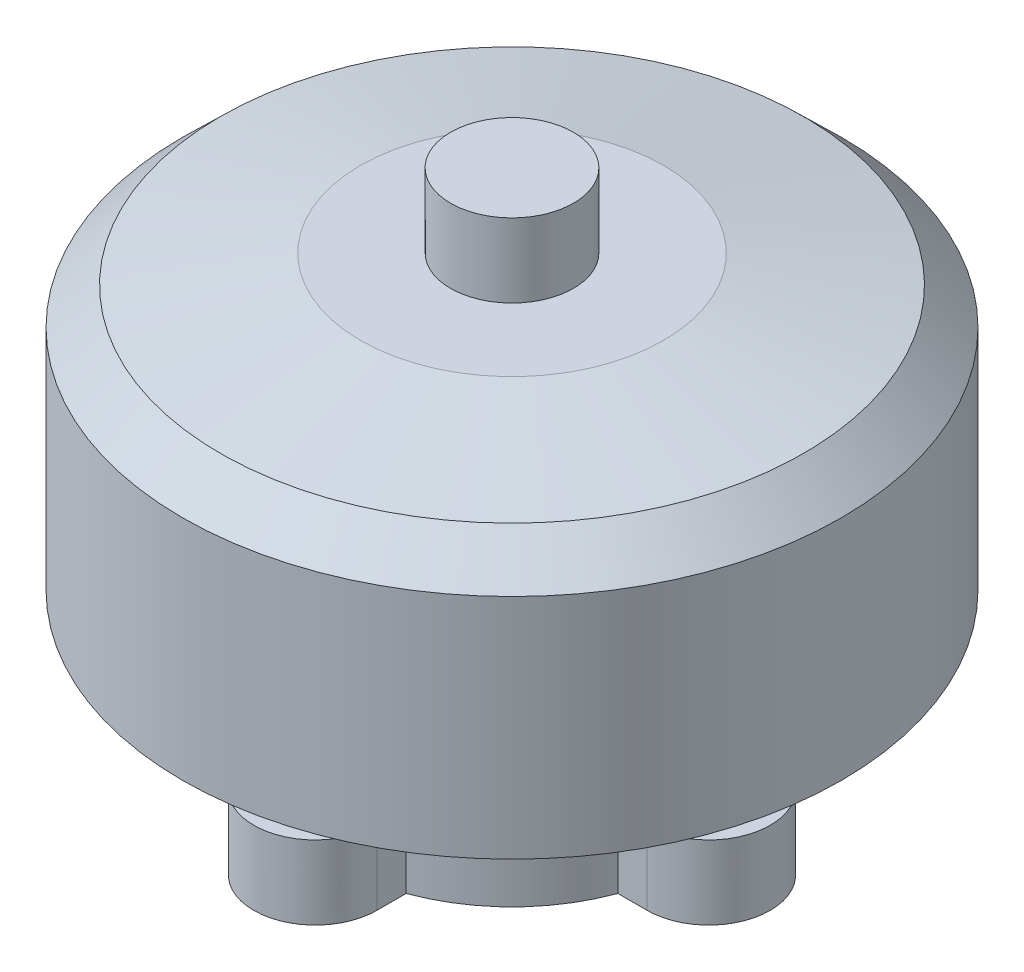
SolidWorks part; units mm, degrees
ref_plane "Спереди" through (0, 0, 0) normal (0, 0, 1) x (1, 0, 0)
ref_plane "Сверху" through (0, 0, 0) normal (0, 1, 0) x (1, 0, 0)
ref_plane "Справа" through (0, 0, 0) normal (1, 0, 0) x (0, 0, -1)
sketch "Эскиз1" plane through (0, 0, 0) normal (0, 1, 0) x (1, 0, 0)
  line L0 (0, 8) -> (0, 6) construction
  line L1 (2.5, 8) -> (2.5, 6)
  line L2 (-2.5, 8) -> (-2.5, 6)
  line L3 (8, 2.5) -> (6, 2.5)
  line L4 (8, -2.5) -> (6, -2.5)
  line L5 (8, 0) -> (6, 0) construction
  line L6 (2.5, -8) -> (2.5, -6)
  line L7 (-2.5, -8) -> (-2.5, -6)
  line L8 (0, -8) -> (0, -6) construction
  line L9 (-8, -2.5) -> (-6, -2.5)
  line L10 (-8, 2.5) -> (-6, 2.5)
  line L11 (-8, 0) -> (-6, 0) construction
  circle A0 centre (0, 0) radius 8 construction
  circle A1 centre (0, 8) radius 1.25
  circle A2 centre (8, 0) radius 1.25
  circle A3 centre (0, -8) radius 1.25
  circle A4 centre (-8, 0) radius 1.25
  circle A5 centre (0, 0) radius 6
  circle A6 centre (0, 0) radius 7.25
  arc A7 (2.5, 8) -> (-2.5, 8) centre (0, 8) ccw
  arc A8 (-2.5, 6) -> (2.5, 6) centre (0, 6) ccw
  arc A9 (8, -2.5) -> (8, 2.5) centre (8, 0) ccw
  arc A10 (6, 2.5) -> (6, -2.5) centre (6, 0) ccw
  arc A11 (-2.5, -8) -> (2.5, -8) centre (0, -8) ccw
  arc A12 (2.5, -6) -> (-2.5, -6) centre (0, -6) ccw
  arc A13 (-8, 2.5) -> (-8, -2.5) centre (-8, 0) ccw
  arc A14 (-6, -2.5) -> (-6, 2.5) centre (-6, 0) ccw
  point P13 (0, 7)
  point P23 (7, 0)
  point P30 (0, -7)
  point P37 (-7, 0)
  point P43 (0, 0)
  dimension "D1" = 16
  dimension "D2" = 2.5
  dimension "D3" = 12
  dimension "D4" = 14.5
  dimension "D5" = 2.5
  dimension "D6" = 4
extrude "Бобышка-Вытянуть1" add sketch "Эскиз1" along normal blind 3 contours A14 L9 A6 L7 A12 A5 | L10 A13 L9 A6 A4 | A5 A8 L1 A6 A1 L2 | L1 A7 L2 A6 A1 | A10 L3 A6 L1 A8 A5 | A14 A5 A8 L2 A6 L10 | L6 A12 A5 L7 A6 A3 | L9 A14 A5 L10 A6 A4 | L3 A10 A5 L4 A6 A2 | A12 L6 A6 L4 A10 A5 | L4 A9 L3 A6 A2 | L7 A11 L6 A6 A3 region at (2.4378, 0, -7.4027) region at (4.5855, 0, -4.5855) region at (0, 0, -6.3965) region at (6.3965, 0, 0) region at (7.4027, 0, -2.4378) region at (-4.5855, 0, -4.5855) region at (-7.0996, 0, -1.7504) region at (-6.3965, 0, 0) region at (4.5855, 0, 4.5855) region at (0, 0, 6.3965) region at (-4.5855, 0, 4.5855) region at (2.4378, 0, 7.4027)
cosmetic thread "Условное изображение резьбы1" parameters "D2"=3
cosmetic thread "Условное изображение резьбы2" parameters "D2"=3
cosmetic thread "Условное изображение резьбы3" parameters "D2"=3
cosmetic thread "Условное изображение резьбы4" parameters "D2"=3
sketch "Эскиз6" plane through (0, 0, 0) normal (0, 0, 1) x (1, 0, 0)
  line L0 (37.7821, 505.6995) -> (251.7821, 505.6995) construction
sketch "Эскиз2" plane through (0, 0, 0) normal (1, 0, 0) x (0, 0, -1)
  line L0 (6, 3) -> (4.2, 4.5)
  line L1 (6, 3) -> (-6, 3) construction
  line L2 (6.8053, 3) -> (2.5, 3) construction
  line L3 (4.2, 4.5) -> (0, 4.5)
  line L4 (0, 4.5) -> (0, 5.5)
  line L5 (0, 5.5) -> (3.8053, 5.5)
  line L6 (3.8053, 5.5) -> (6.8053, 3)
  line L7 (-6, 0) -> (6, 0) construction
  line L8 (6, 3) -> (6.8053, 3)
  dimension "D1" = 4.5
  dimension "D2" = 4.2
  dimension "D3" = 1
revolve "Повернуть1" add sketch "Эскиз2" angle 360 about L4
sketch "Эскиз3" plane through (0, 4.5, 0) normal (0, -1, 0) x (1, 0, 0)
  circle A0 centre (0, 0) radius 1.25
  dimension "D1" = 2.5
extrude "Вырез-Вытянуть1" cut sketch "Эскиз3" against normal through all
sketch "Эскиз4" plane through (0, 0, 2.5) normal (0, 0, 1) x (1, 0, 0)
  line L0 (8.0234, 3) -> (2.8689, 5.5)
  line L1 (9.25, 3) -> (6.7969, 3) construction
  line L2 (3.8053, 5.5) -> (-3.8053, 5.5) construction
  line L4 (6.8053, 3) -> (8.0234, 3)
  line L5 (6.8053, 3) -> (6.3295, 3)
  line L6 (6.3295, 3) -> (2.8689, 5.5)
extrude "Бобышка-Вытянуть2" add sketch "Эскиз4" against normal blind 0.75
mirror "Зеркальное отражение1" about plane through (0, 0, 0) normal (0, 0, 1) of "Бобышка-Вытянуть2"
pattern_circular "Круговой массив1" count 4 over 360 about axis through (0, 5.5, 0) along (0, -1, 0) of "Зеркальное отражение1"
sketch "Эскиз7" plane through (0, 0, 0) normal (0, 0, 1) x (1, 0, 0)
  line L0 (5.3632, 4.2902) -> (5.3632, 6.0305)
  line L1 (8.0234, 3) -> (2.8689, 5.5) construction
  line L2 (5.3632, 6.0305) -> (13.4, 6.0305)
  line L3 (13.4, 6.0305) -> (13.4, 15.2805)
  line L4 (13.4, 15.2805) -> (11.8618, 16.7778)
  line L5 (11.8618, 16.7778) -> (6.1633, 17.9076)
  line L6 (6.1633, 17.9076) -> (0, 17.9076)
  line L7 (0, 17.9076) -> (0, 4.2902)
  line L8 (0, 4.2902) -> (5.3632, 4.2902)
  dimension "D1" = 13.4
  dimension "D2" = 9.25
revolve "Повернуть3" add sketch "Эскиз7" angle 360 about L7
sketch "Эскиз8" plane through (0, 17.9076, 0) normal (0, 1, 0) x (1, 0, 0)
  circle A0 centre (0, 0) radius 2.5
  dimension "D1" = 5
extrude "Бобышка-Вытянуть3" add sketch "Эскиз8" along normal blind 12.3
chamfer "Фаска2" distance 0.5 angle 45 1 edges at (-2.5, 30.2076, 0)
chamfer "Фаска3" distance 0.5 angle 45 4 edges at (0, 0, -6.75) (8, 0, 1.25) (0, 0, 9.25) (-8, 0, 1.25)
sketch "Sketch1" plane through (0, 17.9076, 0) normal (0, 1, 0) x (1, 0, 0)
  circle A0 centre (0, 0) radius 3.2976
extrude "Cut-Extrude1" cut sketch "Sketch1" along normal through all from offset 3
